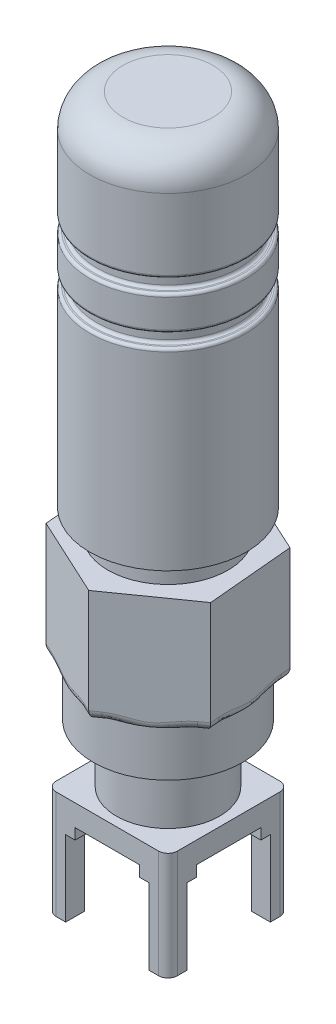
SolidWorks part; units mm, degrees
material "Brass"
ref_plane "Front Plane" through (0, 0, 0) normal (0, 0, 1) x (1, 0, 0)
ref_plane "Top Plane" through (0, 0, 0) normal (0, 1, 0) x (1, 0, 0)
ref_plane "Right Plane" through (0, 0, 0) normal (1, 0, 0) x (0, 0, -1)
sketch "Sketch1" plane through (0, 0, 0) normal (0, 1, 0) x (1, 0, 0)
  line L0 (-3.2, -3.2) -> (3.2, -3.2)
  line L1 (-3.2, -3.2) -> (-3.2, 3.2)
  line L2 (3.2, -3.2) -> (3.2, 3.2)
  line L3 (-3.2, 3.2) -> (3.2, 3.2)
  line L4 (-3.2, -3.2) -> (3.2, 3.2) construction
  line L5 (3.2, -3.2) -> (-3.2, 3.2) construction
  point P1 (0, 0)
  dimension "D1" = 6.4
  dimension "D2" = 6.4
extrude "Boss-Extrude1" add sketch "Sketch1" along normal blind 1.7
sketch "Sketch2" plane through (0, 0, 0) normal (0, -1, 0) x (1, 0, 0)
  line L0 (-3.2, -1.7) -> (-1.7, -1.7)
  line L1 (-3.2, -1.7) -> (-3.2, 1.7)
  line L2 (3.2, -1.7) -> (3.2, 1.7)
  line L3 (-3.2, 1.7) -> (-1.7, 1.7)
  line L4 (-3.2, -1.7) -> (3.2, 1.7) construction
  line L5 (3.2, -1.7) -> (-3.2, 1.7) construction
  line L6 (-3.2, -3.2) -> (-3.2, 3.2) construction
  line L7 (-1.7, 3.2) -> (-1.7, 1.7)
  line L8 (-1.7, 3.2) -> (1.7, 3.2)
  line L9 (-1.7, -3.2) -> (1.7, -3.2)
  line L10 (1.7, 3.2) -> (1.7, 1.7)
  line L11 (-1.7, 3.2) -> (1.7, -3.2) construction
  line L12 (-1.7, -3.2) -> (1.7, 3.2) construction
  line L13 (-3.2, 3.2) -> (3.2, 3.2) construction
  line L14 (-1.7, -1.7) -> (-1.7, -3.2)
  line L15 (1.7, -1.7) -> (1.7, -3.2)
  line L16 (1.7, -1.7) -> (3.2, -1.7)
  line L17 (1.7, 1.7) -> (3.2, 1.7)
  point P1 (0, 0)
  point P9 (0, 0)
  dimension "D1" = 3.4
  dimension "D2" = 3.4
extrude "Cut-Extrude1" cut sketch "Sketch2" against normal blind 0.57
sketch "Sketch3" plane through (0, 0.57, 0) normal (0, -1, 0) x (1, 0, 0)
  circle A0 centre (0, 0) radius 0.635
extrude "Boss-Extrude2" add sketch "Sketch3" along normal blind 4.57
sketch "Sketch4" plane through (0, 0, 0) normal (0, -1, 0) x (1, 0, 0)
  line L1 (-3.2, 3.2) -> (-2.2, 3.2)
  line L2 (-3.2, 3.2) -> (-3.2, 2.2)
  line L3 (-3.2, 2.2) -> (-2.2, 2.2)
  line L4 (-2.2, 3.2) -> (-2.2, 2.2)
  dimension "D1" = 1
  dimension "D2" = 1
extrude "Boss-Extrude3" add sketch "Sketch4" along normal blind 4
mirror "Mirror3" about plane through (0, 0, 0) normal (0, 0, 1) of "Boss-Extrude3"
mirror "Mirror4" about plane through (0, 0, 0) normal (1, 0, 0) of "Mirror3"
fillet "Fillet1" radius 0.5 4 edges at (-3.2, -1.15, 3.2) (3.2, -1.15, 3.2) (3.2, -1.15, -3.2) (-3.2, -1.15, -3.2)
sketch "Sketch5" plane through (0, 1.7, 0) normal (0, 1, 0) x (1, 0, 0)
  circle A0 centre (0, 0) radius 2.72
extrude "Boss-Extrude4" add sketch "Sketch5" along normal blind 3.07
sketch "Sketch6" plane through (0, 4.77, 0) normal (0, 1, 0) x (1, 0, 0)
  circle A0 centre (0, 0) radius 3.94
extrude "Boss-Extrude5" add sketch "Sketch6" along normal blind 2.4
sketch "Sketch7" plane through (0, 7.17, 0) normal (0, 1, 0) x (1, 0, 0)
  line L1 (0.4174, -4.5999) -> (4.1923, -1.9385)
  line L2 (4.1923, -1.9385) -> (3.775, 2.6614)
  line L3 (3.775, 2.6614) -> (-0.4174, 4.5999)
  line L4 (-0.4174, 4.5999) -> (-4.1923, 1.9385)
  line L5 (-4.1923, 1.9385) -> (-3.775, -2.6614)
  line L6 (-3.775, -2.6614) -> (0.4174, -4.5999)
  circle A0 centre (0, 0) radius 4 construction
extrude "Boss-Extrude6" add sketch "Sketch7" along normal blind 6
fillet "Fillet2" radius 0.5 6 edges at (-1.6788, 7.17, 3.6307) (-3.9836, 7.17, 0.3614) (-2.3048, 7.17, -3.2692) (1.6788, 7.17, -3.6307) (2.3048, 7.17, 3.2692) (3.9836, 7.17, -0.3614)
sketch "Sketch8" plane through (0, 13.17, 0) normal (0, 1, 0) x (1, 0, 0)
  circle A0 centre (0, 0) radius 3.17
extrude "Boss-Extrude7" add sketch "Sketch8" along normal blind 1.3
sketch "Sketch9" plane through (0, 14.47, 0) normal (0, 1, 0) x (1, 0, 0)
  circle A0 centre (0, 0) radius 4.125
extrude "Boss-Extrude8" add sketch "Sketch9" along normal blind 10.15
sketch "Sketch10" plane through (0, 24.62, 0) normal (0, 1, 0) x (1, 0, 0)
  circle A0 centre (0, 0) radius 3.75
extrude "Boss-Extrude9" add sketch "Sketch10" along normal blind 0.7
sketch "Sketch11" plane through (0, 25.32, 0) normal (0, 1, 0) x (1, 0, 0)
  circle A0 centre (0, 0) radius 4.125
extrude "Boss-Extrude10" add sketch "Sketch11" along normal blind 1.8
sketch "Sketch12" plane through (0, 27.12, 0) normal (0, 1, 0) x (1, 0, 0)
  circle A0 centre (0, 0) radius 3.75
extrude "Boss-Extrude11" add sketch "Sketch12" along normal blind 0.7
sketch "Sketch13" plane through (0, 27.82, 0) normal (0, 1, 0) x (1, 0, 0)
  circle A0 centre (0, 0) radius 4.125
extrude "Boss-Extrude12" add sketch "Sketch13" along normal blind 5.65
fillet "Fillet4" radius 1.75 1 edges at (0, 33.47, 4.125)
fillet "Fillet5" radius 0.15 8 edges at (0, 27.82, 3.75) (0, 25.32, 3.75) (0, 27.12, 3.75) (0, 25.32, 4.125) (0, 27.12, 4.125) (0, 27.82, 4.125) (0, 24.62, 4.125) (0, 24.62, 3.75)
